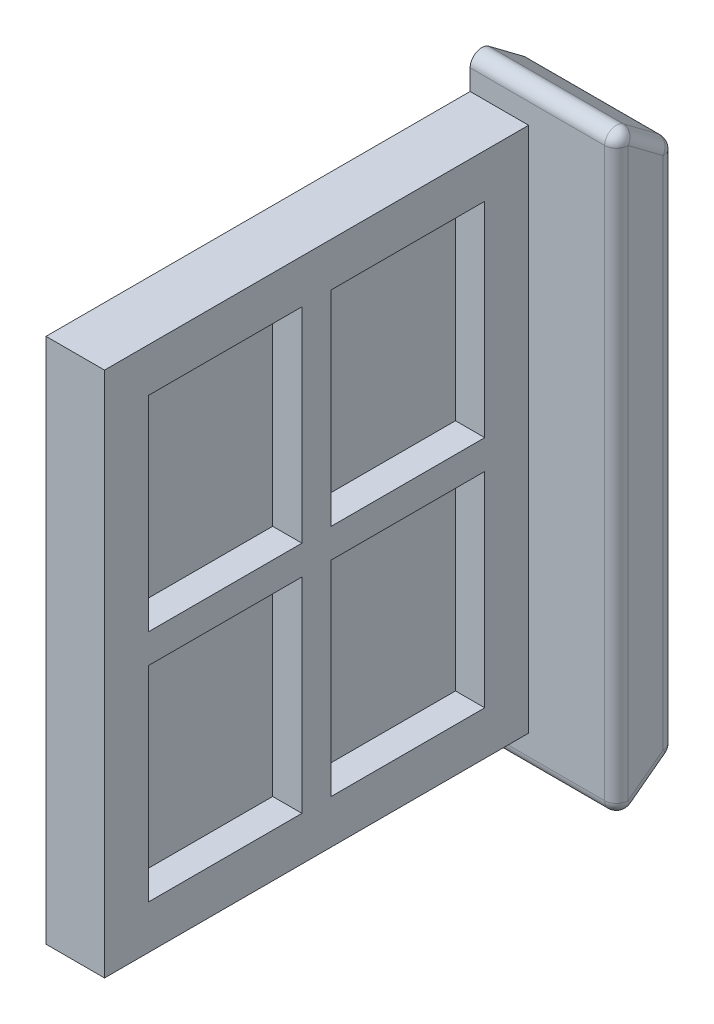
SolidWorks part; units mm, degrees
ref_plane "Alzado" through (0, 0, 0) normal (1, 0, 0) x (0, 1, 0)
ref_plane "Planta" through (0, 0, 0) normal (0, 0, 1) x (0, 1, 0)
ref_plane "Vista lateral" through (0, 0, 0) normal (0, 1, 0) x (-1, 0, 0)
sketch "Croquis2" plane through (0, 0, 0) normal (1, 0, 0) x (0, 1, 0)
  line L1 (-90, 82.5) -> (90, 82.5)
  line L2 (-90, 82.5) -> (-90, -82.5)
  line L3 (-90, -82.5) -> (90, -82.5)
  line L4 (90, 82.5) -> (90, -82.5)
  line L5 (-90, 82.5) -> (90, -82.5) construction
  line L6 (-90, -82.5) -> (90, 82.5) construction
  point P0 (0, 0)
  dimension "D1" = 165
  dimension "D2" = 180
extrude "Saliente-Extruir1" add sketch "Croquis2" along normal blind 20
sketch "Croquis3" plane through (20, 0, 0) normal (1, 0, 0) x (0, 1, 0)
  line L0 (90, -82.5) -> (90, 82.5) construction
  line L1 (-90, 82.5) -> (90, 82.5) construction
  line L2 (-90, 82.5) -> (-90, -62.5) construction
  line L3 (-90, -62.5) -> (90, -62.5) construction
  line L4 (90, 82.5) -> (90, -62.5) construction
  line L5 (0, -62.5) -> (0, 82.5) construction
  line L6 (-90, 10) -> (90, 10) construction
  line L11 (-75, 67.5) -> (-5, 67.5)
  line L12 (75, 67.5) -> (75, 15)
  line L13 (-75, -47.5) -> (-5, -47.5)
  line L14 (-75, 67.5) -> (-75, 15)
  line L15 (-5, -47.5) -> (-5, 5)
  line L16 (5, -47.5) -> (5, 5)
  line L17 (-75, 15) -> (-5, 15)
  line L18 (-75, 5) -> (-5, 5)
  line L19 (5, 5) -> (75, 5)
  line L20 (-5, 15) -> (-5, 67.5)
  line L21 (5, 15) -> (75, 15)
  line L22 (5, 15) -> (5, 67.5)
  line L23 (5, 67.5) -> (75, 67.5)
  line L24 (-75, 67.5) -> (75, 67.5) construction
  line L25 (-75, 5) -> (-75, -47.5)
  line L26 (-75, 67.5) -> (-75, -47.5) construction
  line L27 (75, 5) -> (75, -47.5)
  line L28 (75, 67.5) -> (75, -47.5) construction
  line L29 (5, -47.5) -> (75, -47.5)
  line L30 (-75, -47.5) -> (75, -47.5) construction
  dimension "D1" = 145
  dimension "D3" = 10
  dimension "D4" = 10
  dimension "D2" = 15
extrude "Cortar-Extruir1" cut sketch "Croquis3" against normal blind 10
sketch "Croquis5" plane through (20, 0, 0) normal (1, 0, 0) x (0, 1, 0)
  line L0 (-90, -62.5) -> (-105, -62.5)
  line L1 (-90, -62.5) -> (90, -62.5)
  line L2 (-90, -62.5) -> (-90, -82.5) construction
  line L3 (-90, -82.5) -> (90, -82.5)
  line L4 (90, -62.5) -> (90, -82.5) construction
  line L5 (-105, -62.5) -> (-90, -82.5)
  line L6 (0, -82.5) -> (0, -62.5) construction
  line L7 (105, -62.5) -> (90, -82.5)
  line L8 (90, -62.5) -> (105, -62.5)
  dimension "D1" = 15
extrude "Saliente-Extruir2" add sketch "Croquis5" along normal blind 30 and the other way blind 20
split "Partir1" bodies to split 103 resulting bodies 104 105 split by face at (17.5, 0, -62.5)
ref_plane "Plano1" through (0, 70, 0) normal (0, 1, 0) x (-1, 0, 0)
sketch "Croquis6" plane through (0, 70, 0) normal (0, 1, 0) x (-1, 0, 0)
  line L0 (0, -82.5) -> (0, -102.5)
  line L1 (0, -102.5) -> (-8, -102.5)
  line L3 (-30, -82.5) -> (0, -82.5)
  spline S0 degree 3 poles (-30, -82.5) (-30.1062, -95.4768) (-15.4171, -88.007) (-8, -95.9717) (-8, -102.5) knots 0 0 0 0 0.624829 1 1 1 1
  dimension "D1" = 20
  dimension "D2" = 8
  dimension "D3" = 30
extrude "Saliente-Extruir3" add sketch "Croquis6" against normal blind 10
mirror "Simetría1" about plane through (0, 0, 0) normal (0, 1, 0) of "Saliente-Extruir3"
fillet "Redondeo2" radius 4 18 edges at (15, 60, -82.5) (30, 65, -82.5) (15, 70, -82.5) (4, 60, -102.5) (4, 70, -102.5) (8, 65, -102.5) (4, -70, -102.5) (4, -60, -102.5) (8, -65, -102.5) (30, -65, -82.5) (15, -70, -82.5) (15, -60, -82.5) (50, 0, -82.5) (50, 0, -62.5)
fillet "Redondeo3" radius 4 10 edges at (23, 90, -82.5) (48.8284, 90.8787, -81.3284) (50, 97.5, -72.5) (48.8284, 104.1213, -63.6716) (23, -90, -82.5) (48.8284, -90.8787, -81.3284) (50, -97.5, -72.5) (48.8284, -104.1213, -63.6716) (23, 105, -62.5) (23, -105, -62.5)
